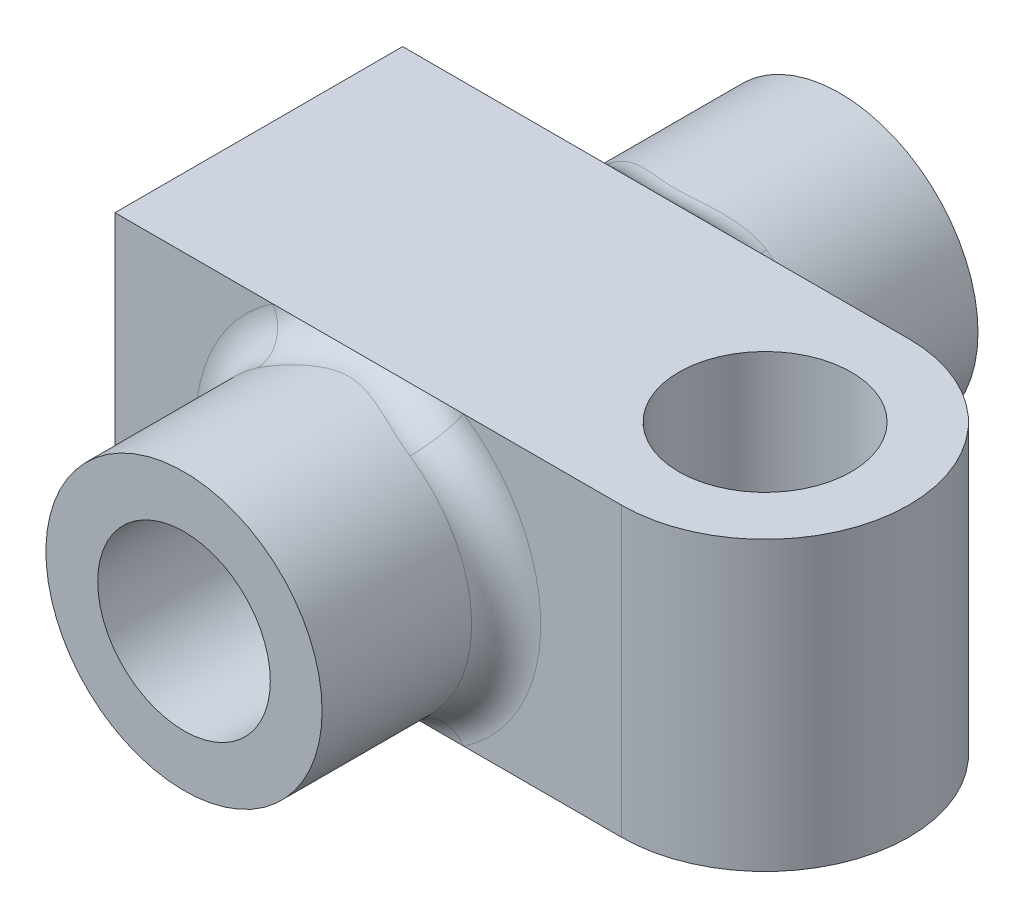
SolidWorks part; units mm, degrees
ref_plane "Front Plane" through (0, 0, 0) normal (0, 0, 1) x (1, 0, 0)
ref_plane "Top Plane" through (0, 0, 0) normal (0, 1, 0) x (1, 0, 0)
ref_plane "Right Plane" through (0, 0, 0) normal (1, 0, 0) x (0, 0, -1)
sketch "Sketch1" plane through (0, 0, 0) normal (0, 1, 0) x (1, 0, 0)
  line L1 (0, 0) -> (44, 0)
  line L2 (0, 0) -> (0, 25)
  line L3 (0, 25) -> (44, 25)
  arc A0 (44, 0) -> (44, 25) centre (44, 12.5) ccw
  circle A1 centre (44, 12.5) radius 7.5
  dimension "D3" = 15
  dimension "D1" = 25
  dimension "D2" = 44
extrude "Boss-Extrude1" add sketch "Sketch1" along normal mid plane 25
ref_plane "Plane2" through (0, 0, -12.5) normal (0, 0, 1) x (1, 0, 0)
sketch "Sketch2" plane through (0, 0, -12.5) normal (0, 0, 1) x (1, 0, 0)
  line L0 (0, 0) -> (44, 0) construction
  line L1 (44, 12.5) -> (44, -12.5) construction
  line L2 (22, 0) -> (22, 12.5) construction
  line L3 (0, 12.5) -> (44, 12.5) construction
  line L4 (0, 12.5) -> (0, -12.5) construction
  circle A0 centre (22, 0) radius 12
  dimension "D2" = 24
  dimension "D1" = 22
extrude "Boss-Extrude2" add sketch "Sketch2" along normal mid plane 57
sketch "Sketch4" plane through (0, 0, 0) normal (-1, 0, 0) x (0, 0, 1)
  line L0 (-12.5, -13.75) -> (-12.5, 13.75) construction
  circle A0 centre (-12.5, 0) radius 7.5
  dimension "D1" = 15
extrude "Boss-Extrude3" add sketch "Sketch4" along normal blind 3
sketch "Sketch5" plane through (0, 0, -41) normal (0, 0, -1) x (-1, 0, 0)
  circle A0 centre (-22, 0) radius 7.5
  circle A1 centre (-22, 0) radius 12 construction
  dimension "D1" = 15
extrude "Cut-Extrude1" cut sketch "Sketch5" against normal blind 69
fillet "Fillet1" radius 3 3 edges at (34, 0, -25) (10, 0, 0) (0, 0, -5)
hole_wizard "M6x1.0 Tapped Hole1" positions "Sketch6" profile "Sketch7" tap size "M6x1.0" standard "ANSI Metric"
sketch "Sketch6" plane through (-3, 0, 0) normal (-1, 0, 0) x (0, 0, 1)
  point P0 (-12.5, 0)
sketch "Sketch7" plane through (-3, 0, -12.5) normal (0, 1, 0) x (0, 0, 1)
  line L0 (0, 0) -> (0, 21.5022)
  line L1 (0, 21.5022) -> (2.5, 20)
  line L2 (2.5, 20) -> (2.5, 0.525)
  line L3 (2.5, 0.525) -> (3.025, 0)
  line L5 (3.025, 0) -> (0, 0)
  line L6 (-2.5, 0.525) -> (-3.025, 0) construction
  line L10 (0, 21.5022) -> (-2.5, 20) construction
  line L11 (0, -6.35) -> (0, 107.95) construction
  dimension "Tap Drill Dia." = 5
  dimension "Tap Drill Depth" = 20
  dimension "Near C'Sink Dia." = 6.05
  dimension "Near C'Sink Angle" = 90
  dimension "Drill Angle" = 118
cosmetic thread "Hole Thread1" parameters "D1"=1900, "D2"=6
